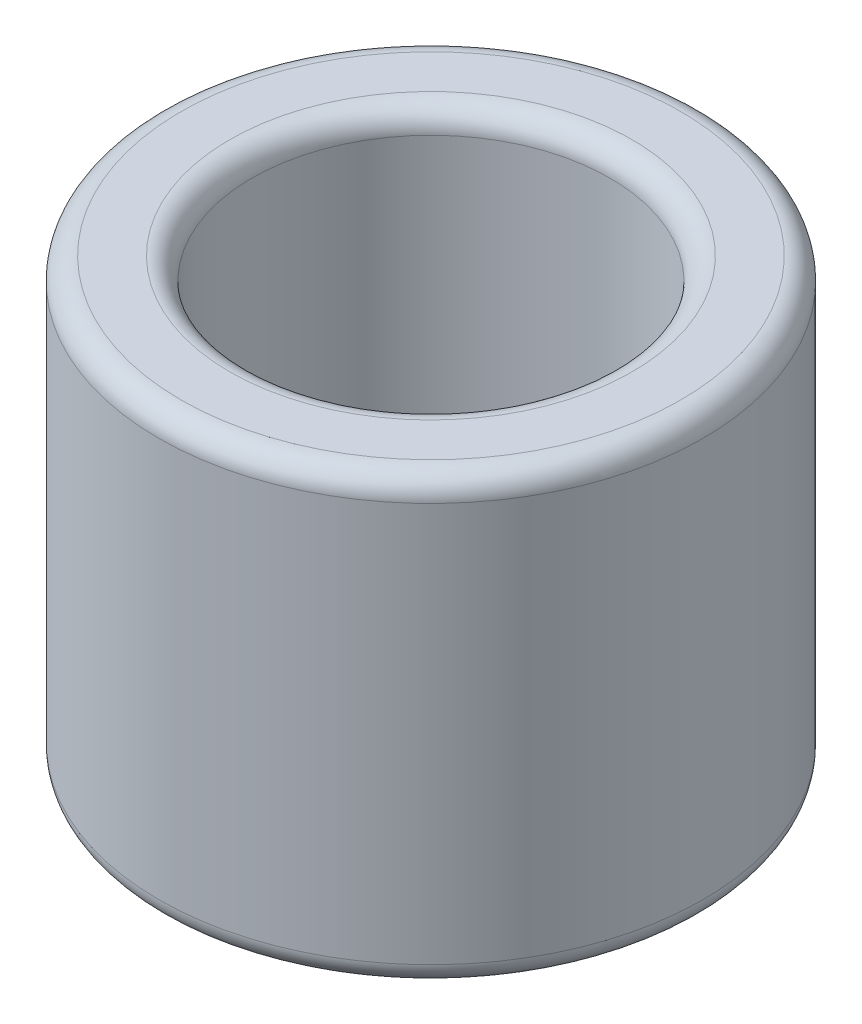
SolidWorks part; units mm, degrees
ref_plane "Front Plane" through (0, 0, 0) normal (0, 0, 1) x (1, 0, 0)
ref_plane "Top Plane" through (0, 0, 0) normal (0, 1, 0) x (1, 0, 0)
ref_plane "Right Plane" through (0, 0, 0) normal (1, 0, 0) x (0, 0, -1)
sketch "Sketch2" plane through (0, 0, 0) normal (0, 1, 0) x (1, 0, 0)
  circle A0 centre (0, 0) radius 3.175
  circle A1 centre (0, 0) radius 4.826
  dimension "OD" = 9.652
  dimension "ID" = 6.35
extrude "Spacer" add sketch "Sketch2" along normal blind 7.874
fillet "Fillet" radius 0.3937 4 edges at (0, 0, 3.175) (0, 0, 4.826) (0, 7.874, 3.175) (0, 7.874, 4.826)
equation "\"OD@Sketch2\" = .38in"
equation "\"ID@Sketch2\"=.25in"
equation "\"D1@Spacer\" = .31in"
equation "\"D1@Fillet\"=\"D1@Spacer\" / 20"
